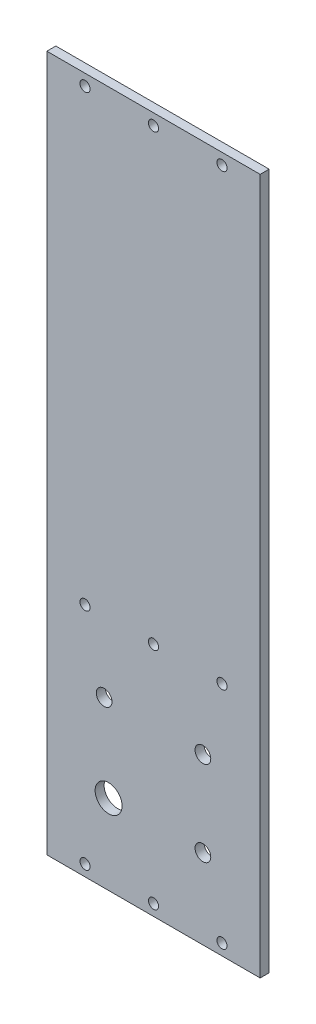
SolidWorks part; units mm, degrees
ref_plane "Piano frontale" through (0, 0, 0) normal (0, 0, 1) x (1, 0, 0)
ref_plane "Piano superiore" through (0, 0, 0) normal (0, 1, 0) x (1, 0, 0)
ref_plane "Piano destro" through (0, 0, 0) normal (1, 0, 0) x (0, 0, -1)
sketch "Schizzo1" plane through (0, 0, 0) normal (0, 0, 1) x (1, 0, 0)
  line L1 (0, 0) -> (95, 0)
  line L2 (0, 0) -> (0, 310)
  line L3 (0, 310) -> (95, 310)
  line L4 (95, 0) -> (95, 310)
  line L5 (0, 105) -> (95, 105) construction
  line L6 (95, 5) -> (0, 5) construction
  line L7 (0, 35.6) -> (95, 35.6) construction
  line L8 (0, 73.5) -> (95, 73.5) construction
  line L9 (95, 155) -> (0, 155) construction
  circle A0 centre (78, 5) radius 2.25
  circle A1 centre (47.5, 5) radius 2.25
  circle A2 centre (17, 5) radius 2.25
  circle A3 centre (17, 305) radius 2.25
  circle A4 centre (47.5, 305) radius 2.25
  circle A5 centre (78, 305) radius 2.25
  circle A6 centre (69.5, 35.6) radius 3.5
  circle A7 centre (27.5, 35.6) radius 6
  circle A8 centre (25.5, 73.5) radius 3.5
  circle A9 centre (69.5, 73.5) radius 3.5
  circle A10 centre (47.5, 105) radius 2.25
  circle A11 centre (78, 105) radius 2.25
  circle A12 centre (17, 105) radius 2.25
  dimension "D4" = 4.5
  dimension "D10" = 7
  dimension "D11" = 12
  dimension "D1" = 95
  dimension "D2" = 310
  dimension "D3" = 5
  dimension "D5" = 35.6
  dimension "D6" = 73.5
  dimension "D7" = 27.5
  dimension "D8" = 69.5
  dimension "D9" = 25.5
  dimension "D14" = 105
extrude "Estrusione-Estrusione1" add sketch "Schizzo1" against normal blind 4
